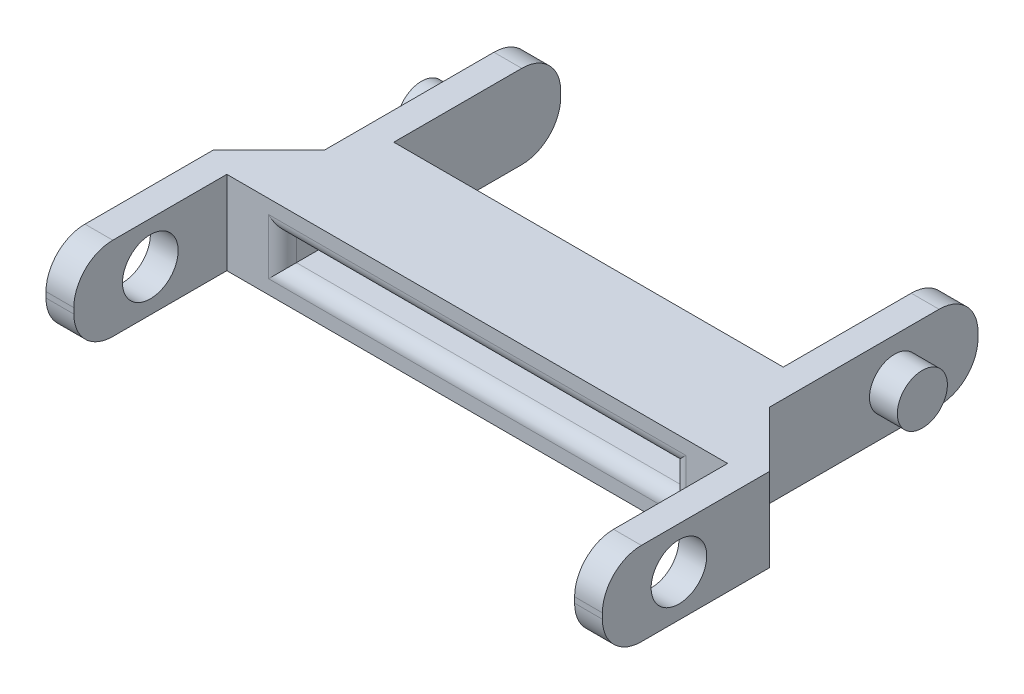
SolidWorks part; units mm, degrees
ref_plane "Front Plane" through (0, 0, 0) normal (0, 0, 1) x (1, 0, 0)
ref_plane "Top Plane" through (0, 0, 0) normal (0, 1, 0) x (1, 0, 0)
ref_plane "Right Plane" through (0, 0, 0) normal (1, 0, 0) x (0, 0, -1)
sketch "Sketch1" plane through (0, 0, 0) normal (0, 0, 1) x (1, 0, 0)
  line L1 (7, -0.5) -> (-7, -0.5)
  line L2 (7, -0.5) -> (7, 0.5)
  line L3 (7, 0.5) -> (-7, 0.5)
  line L4 (-7, -0.5) -> (-7, 0.5)
  line L5 (7, -0.5) -> (-7, 0.5) construction
  line L6 (7, 0.5) -> (-7, -0.5) construction
  point P0 (0, 0)
  dimension "D1" = 14
  dimension "D2" = 1
extrude "Extrude-Thin1" add sketch "Sketch1" along normal mid plane 4 thin thin type one direction wall 1
sketch "Sketch2" plane through (8, 0, 0) normal (1, 0, 0) x (0, 0, -1)
  line L0 (-2, 1.5) -> (2, 1.5) construction
  line L1 (-1.5, 1.5) -> (-7.5, 1.5)
  line L2 (-1.5, 1.5) -> (-1.5, -1.5)
  line L3 (-1.5, -1.5) -> (-7.5, -1.5)
  line L4 (-7.5, 1.5) -> (-7.5, -1.5)
  line L5 (-2, -1.5) -> (2, -1.5) construction
  dimension "D1" = 1.5
  dimension "D2" = 6
extrude "Boss-Extrude1" add sketch "Sketch2" along normal blind 2
chamfer "Chamfer3" distance 2 angle 45 1 edges at (8, 0, 1.5)
sketch "Sketch3" plane through (8, 0, 0) normal (-1, 0, 0) x (0, 0, 1)
  line L1 (7.5, 1.5) -> (2, 1.5)
  line L2 (7.5, 1.5) -> (7.5, -1.5)
  line L3 (7.5, -1.5) -> (2, -1.5)
  line L4 (2, 1.5) -> (2, -1.5)
extrude "Cut-Extrude1" cut sketch "Sketch3" against normal blind 1
sketch "Sketch4" plane through (8, 0, 0) normal (1, 0, 0) x (0, 0, -1)
  line L0 (0.5, -1.5) -> (2, -1.5) construction
  line L1 (2, 1.5) -> (8, 1.5)
  line L2 (2, 1.5) -> (2, -1.5)
  line L3 (2, -1.5) -> (8, -1.5)
  line L4 (8, 1.5) -> (8, -1.5)
  dimension "D1" = 6
extrude "Boss-Extrude2" add sketch "Sketch4" against normal up to surface (1 mm away) up to face at (7, 0, 0)
mirror "Mirror2" about plane through (0, 0, 0) normal (1, 0, 0) of "Cut-Extrude1", "Boss-Extrude1"
sketch "Sketch5" plane through (-8, 0, 0) normal (-1, 0, 0) x (0, 0, 1)
  line L0 (1.5, -1.5) -> (-2, -1.5) construction
  line L1 (-2, 1.5) -> (-8, 1.5)
  line L2 (-2, 1.5) -> (-2, -1.5)
  line L3 (-2, -1.5) -> (-8, -1.5)
  line L4 (-8, 1.5) -> (-8, -1.5)
extrude "Boss-Extrude3" add sketch "Sketch5" against normal up to surface (1 mm away) up to face at (-7, 0, 0)
chamfer "Chamfer4" distance 2 angle 45 1 edges at (-8, 0, 1.5)
fillet "Fillet1" radius 1.4 8 edges at (9.5, -1.5, 7.5) (9.5, 1.5, 7.5) (-9.5, -1.5, 7.5) (-9.5, 1.5, 7.5) (-7.5, -1.5, -8) (-7.5, 1.5, -8) (7.5, -1.5, -8) (7.5, 1.5, -8)
sketch "Sketch7" plane through (9, 0, 0) normal (-1, 0, 0) x (0, 0, 1)
  line L0 (2, 0) -> (7.5, 0) construction
  line L1 (2, 1.5) -> (2, -1.5) construction
  line L2 (7.5, -0.1) -> (7.5, 0.1) construction
  circle A0 centre (4.75, 0) radius 1
extrude "Cut-Extrude3" cut sketch "Sketch7" against normal blind 1
mirror "Mirror6" about plane through (0, 0, 0) normal (1, 0, 0) of "Cut-Extrude3"
sketch "Sketch8" plane through (-7, 0, 0) normal (1, 0, 0) x (0, 0, -1)
  line L0 (2, 0.5) -> (2, -0.5) construction
  line L1 (2, 0) -> (8, 0) construction
  line L2 (8, 0.1) -> (8, -0.1) construction
  circle A0 centre (5, 0) radius 0.9
extrude "Boss-Extrude5" add sketch "Sketch8" against normal blind 2
mirror "Mirror7" about plane through (0, 0, 0) normal (1, 0, 0) of "Boss-Extrude5"
fillet "Fillet4" radius 0.5 2 edges at (0, -0.5, -2) (0, 0.5, -2)
fillet "Fillet6" radius 0.5 4 edges at (7, 0, 2) (0, -0.5, 2) (-7, 0, 2) (0, 0.5, 2)
